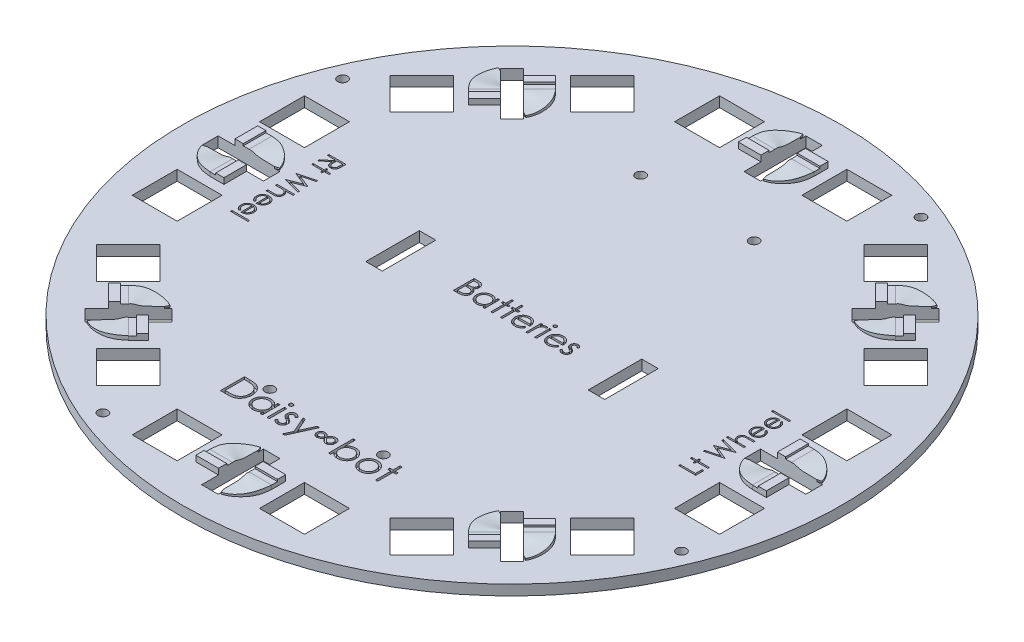
SolidWorks part; units mm, degrees
ref_plane "Front" through (0, 0, 0) normal (0, 0, 1) x (1, 0, 0)
ref_plane "Top" through (0, 0, 0) normal (0, 1, 0) x (1, 0, 0)
ref_plane "Right" through (0, 0, 0) normal (1, 0, 0) x (0, 0, -1)
sketch "Sketch1" plane through (0, 0, 0) normal (0, 1, 0) x (1, 0, 0)
  circle A0 centre (0, 0) radius 101.6
  dimension "D1" = 203.2
extrude "Boss-Extrude1" add sketch "Sketch1" along normal blind 3.175 contours A0
sketch "Sketch2" plane through (0, 3.175, 0) normal (0, 1, 0) x (1, 0, 0)
  line L1 (-2.54, -93.1333) -> (2.54, -93.1333)
  line L2 (-2.54, -93.1333) -> (-2.54, -74.0833)
  line L3 (-2.54, -74.0833) -> (2.54, -74.0833)
  line L4 (2.54, -93.1333) -> (2.54, -74.0833)
  circle A0 centre (0, 0) radius 101.6 construction
  point P4 (0, -74.0833)
  dimension "D1" = 5.08
  dimension "D2" = 19.05
  dimension "D3" = 93.1333
extrude "Cut-Extrude1" cut sketch "Sketch2" against normal up to next and the other way through all contours L1 L4 L3 L2
sketch "Sketch4" plane through (0, 3.175, 0) normal (0, 1, 0) x (1, 0, 0)
  line L0 (0, -83.6083) -> (-2.9434, -74.5495) construction
  line L1 (-2.9434, -74.5495) -> (0, -83.6083) construction
  line L2 (0, -83.6083) -> (-5.5987, -75.9025) construction
  line L3 (0, -83.6083) -> (-7.7059, -78.0097) construction
  line L4 (0, -83.6083) -> (-9.0588, -80.665) construction
  line L5 (0, -83.6083) -> (-9.525, -83.6083) construction
  line L9 (2.54, -74.0833) -> (-2.54, -74.0833) construction
  line L10 (2.54, -74.0833) -> (2.54, -93.1333) construction
  line L11 (-2.54, -74.0833) -> (-2.54, -93.1333) construction
  line L12 (2.54, -93.1333) -> (-2.54, -93.1333) construction
  circle A0 centre (0, -83.6083) radius 9.525 construction
  point P16 (0, -74.0833)
  point P19 (2.54, -83.6083)
  dimension "D1" = 18
  dimension "D2" = 18
  dimension "D3" = 18
  dimension "D4" = 18
  dimension "D5" = 18
ref_plane "Plane1" through (-24.5719, 0, 7.9839) normal (0.9511, 0, -0.309) x (-0.309, 0, -0.9511)
ref_plane "Plane2" through (-39.7581, 0, 28.886) normal (0.809, 0, -0.5878) x (-0.5878, 0, -0.809)
ref_plane "Plane3" through (-39.7581, 0, 54.7224) normal (0.5878, 0, -0.809) x (-0.809, 0, -0.5878)
ref_plane "Plane4" through (-24.5719, 0, 75.6245) normal (0.309, 0, -0.9511) x (-0.9511, 0, -0.309)
ref_plane "Plane5" through (0, 0, 83.6083) normal (0, 0, -1) x (-1, 0, 0)
sketch "Sketch5" plane through (-24.5719, 0, 7.9839) normal (0.9511, 0, -0.309) x (-0.309, 0, -0.9511)
  line L0 (-69.6725, 3.175) -> (-87.7902, 3.175) construction
  line L1 (-71.2966, 3.175) -> (-69.9913, 3.175)
  line L2 (-71.2966, 3.175) -> (-71.2966, 3.683)
  line L3 (-71.2966, 3.683) -> (-69.9913, 3.683)
  line L4 (-69.9913, 3.175) -> (-69.9913, 3.683)
  dimension "D2" = 0.508
sketch "Sketch6" plane through (-39.7581, 0, 28.886) normal (0.809, 0, -0.5878) x (-0.5878, 0, -0.809)
  line L0 (-58.4417, 3.175) -> (-73.8535, 3.175) construction
  line L1 (-63.3193, 3.175) -> (-58.1156, 3.175)
  line L2 (-63.3193, 3.175) -> (-63.3193, 3.775)
  line L3 (-63.3193, 3.775) -> (-58.1156, 3.775)
  line L4 (-58.1156, 3.175) -> (-58.1156, 3.775)
  dimension "D2" = 0.6
sketch "Sketch7" plane through (-39.7581, 0, 54.7224) normal (0.5878, 0, -0.809) x (-0.809, 0, -0.5878)
  line L0 (-41.4902, 3.175) -> (-52.6875, 3.175) construction
  line L1 (-46.0041, 3.175) -> (-39.6188, 3.175)
  line L2 (-46.0041, 3.175) -> (-46.0041, 4.075)
  line L3 (-46.0041, 4.075) -> (-39.6188, 4.075)
  line L4 (-39.6188, 3.175) -> (-39.6188, 4.075)
  dimension "D2" = 0.9
sketch "Sketch10" plane through (-24.5719, 0, 75.6245) normal (0.309, 0, -0.9511) x (-0.9511, 0, -0.309)
  line L0 (-25.8364, 3.175) -> (-16.7776, 3.175) construction
  line L1 (-23.1657, 3.175) -> (-16.3114, 3.175)
  line L2 (-23.1657, 3.175) -> (-23.1657, 4.375)
  line L3 (-23.1657, 4.375) -> (-16.3114, 4.375)
  line L4 (-16.3114, 3.175) -> (-16.3114, 4.375)
  dimension "D3" = 1.2
sketch "Sketch11" plane through (0, 0, 83.6083) normal (0, 0, -1) x (-1, 0, 0)
  line L0 (0, 3.175) -> (9.525, 3.175) construction
  line L1 (2.54, 3.175) -> (9.525, 3.175)
  line L2 (2.54, 3.175) -> (2.54, 4.375)
  line L3 (2.54, 4.375) -> (9.525, 4.375)
  line L4 (9.525, 3.175) -> (9.525, 4.375)
  dimension "D3" = 1.2
loft "Loft1" add profiles "Sketch5", "Sketch6", "Sketch7", "Sketch10", "Sketch11" connector at (-2.54, 3.683, 75.791) connector at (-2.54, 3.775, 80.1123) connector at (-2.54, 4.075, 81.7629) connector at (-2.54, 4.375, 82.783) connector at (-2.54, 4.375, 83.6083)
sketch "Sketch13" plane through (-104.9799, 0, 83.6083) normal (0, 0, -1) x (-1, 0, 0)
  line L6 (-95.4549, 3.175) -> (-102.4399, 3.175)
  line L7 (-95.4549, 3.175) -> (-95.4549, 4.375)
  line L8 (-95.4549, 4.375) -> (-102.4399, 4.375)
  line L9 (-102.4399, 3.175) -> (-102.4399, 4.375)
extrude "Boss-Extrude4" add sketch "Sketch13" against normal blind 1.7907
sketch "Sketch25" plane through (0, 0, 85.399) normal (0, 0, 1) x (1, 0, 0)
  line L0 (-9.525, 4.375) -> (-2.54, 4.375) construction
  line L1 (-9.525, 3.175) -> (-2.54, 3.175)
  line L2 (-9.525, 3.175) -> (-9.525, 4.975)
  line L3 (-9.525, 4.975) -> (-2.54, 4.975)
  line L4 (-2.54, 3.175) -> (-2.54, 4.975)
  dimension "D1" = 0.6
extrude "Boss-Extrude5" add sketch "Sketch25" along normal blind 2.54
sketch "Sketch14" plane through (-2.54, 0, 0) normal (1, 0, 0) x (0, 0, -1)
  line L0 (-83.6083, 3.175) -> (-83.6083, 0) construction
  line L1 (-74.0833, 0) -> (-93.1333, 0) construction
ref_plane "Plane6" through (0, 0, 0) normal (1, 0, 0) x (0, 0, -1)
sketch "Sketch15" plane through (0, 0, 0) normal (1, 0, 0) x (0, 0, -1)
  line L0 (-83.6083, 0) -> (-83.6083, 3.175) construction
pattern_circular "CirPattern1" count 2 over 360 about axis through (0, 0, 83.6083) along (0, 1, 0) of "Loft1", "Boss-Extrude5", "Boss-Extrude4" reverse direction yes
ref_axis "Axis1" through (0, 50, 0) along (0, -1, 0)
pattern_circular "CirPattern5" count 8 over 360 about axis through (0, 50, 0) along (0, -1, 0) of "CirPattern1", "Cut-Extrude1"
sketch "Sketch18" plane through (0, 3.175, 0) normal (0, 1, 0) x (1, 0, 0)
  line L4 (0, -101.6) -> (0, 101.6) construction
  line L5 (0, -1.7463) -> (0, 1.7463) construction
  line L6 (-101.6, 0) -> (101.6, 0) construction
  circle A8 centre (0, 0) radius 101.6 construction
sketch "Sketch19" plane through (0, 3.175, 0) normal (0, 1, 0) x (1, 0, 0)
  line L0 (-36.9366, -89.1729) -> (0, 0) construction
  line L1 (0, -101.6) -> (0, 101.6) construction
  circle A1 centre (-36.9366, -89.1729) radius 1.5
  dimension "D1" = 96.52
  dimension "D4" = 3
  dimension "D5" = 22.5
extrude "Cut-Extrude2" cut sketch "Sketch19" against normal through all
pattern_circular "CirPattern7" count 4 over 360 about axis through (0, 50, 0) along (0, -1, 0) of "Cut-Extrude2"
sketch "Sketch23" plane through (0, 3.175, 0) normal (0, 1, 0) x (1, 0, 0)
  line L9 (-2.54, -87.939) -> (-2.54, -93.1333) construction
  line L10 (-26.5557, -76.6805) -> (-12.7, -76.6805)
  line L11 (-26.5557, -76.6805) -> (-26.5557, -90.5362)
  line L16 (-26.5557, -90.5362) -> (-12.7, -90.5362)
  line L17 (-12.7, -76.6805) -> (-12.7, -90.5362)
  line L19 (2.54, -74.0833) -> (2.54, -79.2776) construction
  line L20 (0, -50) -> (0, 50) construction
  line L21 (12.7, -76.6805) -> (12.7, -90.5362)
  line L22 (26.5557, -90.5362) -> (12.7, -90.5362)
  line L23 (26.5557, -76.6805) -> (26.5557, -90.5362)
  line L24 (26.5557, -76.6805) -> (12.7, -76.6805)
  point P8 (-2.54, -90.5362)
  point P9 (2.54, -76.6805)
  dimension "D2" = 10.16
extrude "Cut-Extrude6" cut sketch "Sketch23" against normal through all
pattern_circular "CirPattern8" count 8 over 360 about axis through (0, 50, 0) along (0, -1, 0) of "Cut-Extrude6"
sketch "Sketch16" plane through (0, 3.175, 0) normal (0, 1, 0) x (1, 0, 0)
  line L1 (-16.4163, -2.4279) -> (16.4163, -2.4279) construction
  line L2 (0, -101.6) -> (0, 101.6) construction
  line L3 (-71.12, 15.3104) -> (-71.12, -15.3104) construction
  line L4 (-101.6, 0) -> (101.6, 0) construction
  line L5 (71.12, 15.3104) -> (71.12, -15.3104) construction
  line L6 (-25.719, -65.1065) -> (25.719, -65.1065) construction
  circle A1 centre (0, 0) radius 101.6 construction
  text T0 "Daisy∞bot\r\n" font "Century Gothic" height in points 28
  text T1 "Batteries"
  text T2 "Rt Wheel\r\n" font "Century Gothic" height in points 20
  text T3 "Lt Wheel" font "Century Gothic" height in points 20
  point P4 (-71.12, 0)
  point P7 (0, -65.1065)
  point P10 (0, -2.4279)
  point P15 (71.12, 0)
  dimension "D1" = 32.8326
  dimension "D2" = 30.6207
  dimension "D3" = 51.438
  dimension "D4" = 71.12
  dimension "D5" = 71.12
extrude "Cut-Extrude4" cut sketch "Sketch16" against normal blind 1.27
sketch "Sketch26" plane through (0, 3.175, 0) normal (0, 1, 0) x (1, 0, 0)
  line L0 (-101.6, 0) -> (101.6, 0) construction
  line L1 (-36.83, 8.255) -> (-31.75, 8.255)
  line L2 (-36.83, 8.255) -> (-36.83, -8.255)
  line L3 (-36.83, -8.255) -> (-31.75, -8.255)
  line L4 (-31.75, 8.255) -> (-31.75, -8.255)
  line L5 (0, -101.6) -> (0, 101.6) construction
  point P4 (-36.83, 0)
  dimension "D1" = 16.51
  dimension "D2" = 5.08
  dimension "D3" = 31.75
extrude "Cut-Extrude7" cut sketch "Sketch26" against normal through all
mirror "Mirror1" about plane through (0, 0, 0) normal (1, 0, 0) of "Cut-Extrude7"
sketch "Sketch27" plane through (0, 0, 0) normal (0, -1, 0) x (1, 0, 0)
  line L0 (0, 101.6) -> (0, -101.6) construction
  line L1 (-101.6, 0) -> (101.6, 0) construction
  circle A0 centre (-17.5, -57.15) radius 1.5
  circle A1 centre (-89.1729, -36.9366) radius 1.5 construction
  dimension "D1" = 17.5
  dimension "D2" = 57.15
extrude "Cut-Extrude8" cut sketch "Sketch27" against normal through all both and the other way through all
mirror "Mirror2" about plane through (0, 0, 0) normal (0, 0, 1) of "Cut-Extrude8"
mirror "Mirror3" about plane through (0, 0, 0) normal (1, 0, 0) of "Mirror2"
sketch "Sketch28" plane through (0, 0, 0) normal (0, -1, 0) x (1, 0, 0)
  line L0 (-21.8435, -50.8) -> (21.8435, -50.8) construction
  line L1 (0, 101.6) -> (0, -101.6) construction
  line L2 (-101.6, 0) -> (101.6, 0) construction
  line L3 (-19.568, 50.8) -> (19.568, 50.8) construction
  text T0 "Bk Caster"
  text T1 "Ft Caster"
  point P3 (0, 50.8)
  point P4 (0, -50.8)
  dimension "D1" = 50.8
  dimension "D2" = 50.8
extrude "Cut-Extrude9" cut sketch "Sketch28" against normal blind 1.27
